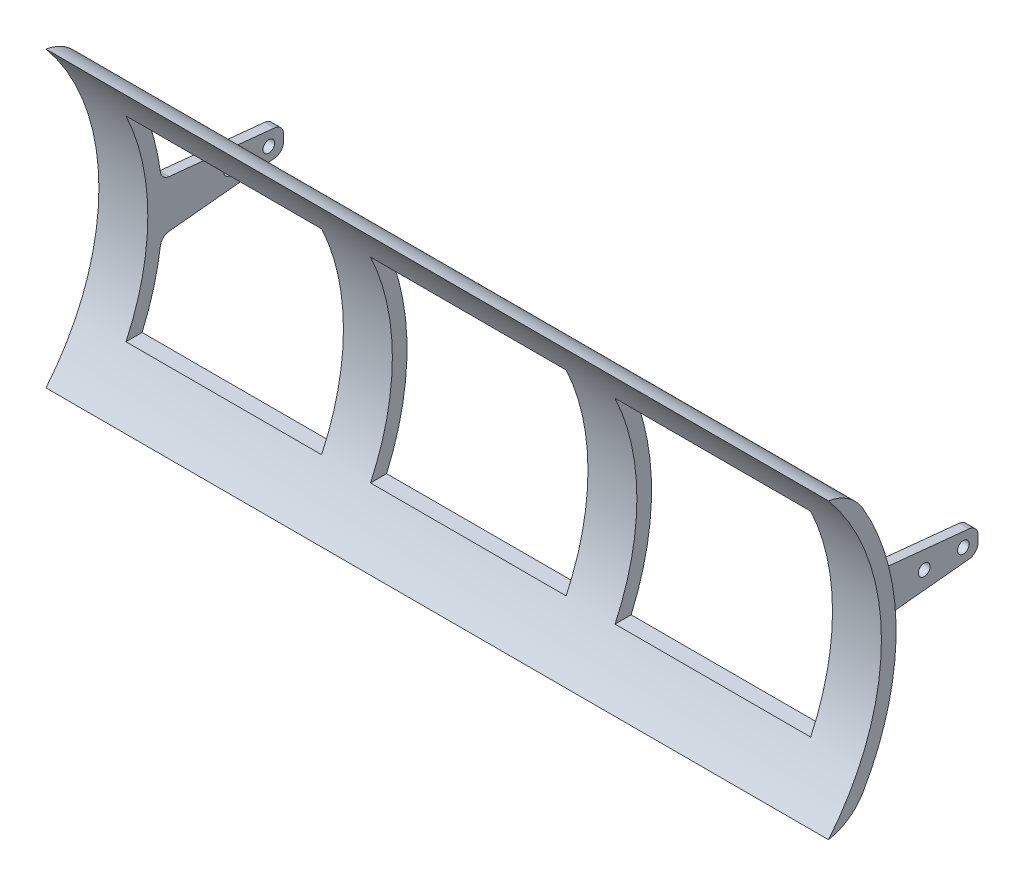
SolidWorks part; units mm, degrees
ref_plane "Front" through (0, 0, 0) normal (0, 0, 1) x (1, 0, 0)
ref_plane "Top" through (0, 0, 0) normal (0, 1, 0) x (1, 0, 0)
ref_plane "Right" through (0, 0, 0) normal (1, 0, 0) x (0, 0, -1)
sketch "Sketch1" plane through (0, 0, 0) normal (1, 0, 0) x (0, 0, -1)
  line L0 (50.8, -38.1) -> (45.9487, -38.1)
  line L1 (45.9487, 38.1) -> (50.8, 38.1)
  arc A0 (45.9487, 38.1) -> (45.9487, -38.1) centre (0, 0) cw
  arc A1 (50.8, 38.1) -> (50.8, -38.1) centre (0, 0) cw
  dimension "D1" = 59.69
  dimension "D3" = 63.5
  dimension "D2" = 76.2
extrude "Boss-Extrude1" add sketch "Sketch1" along normal mid plane 203.2
sketch "Sketch2" plane through (0, 0, 0) normal (0, 0, 1) x (1, 0, 0)
  line L0 (-38.1, -25.4) -> (-38.1, 25.4)
  line L1 (-88.9, -25.4) -> (-38.1, -25.4)
  line L2 (-88.9, -25.4) -> (-88.9, 25.4)
  line L3 (-88.9, 25.4) -> (-38.1, 25.4)
  line L4 (88.9, -25.4) -> (88.9, 25.4)
  line L7 (-25.4, -25.4) -> (-25.4, 25.4)
  line L8 (0, 25.4) -> (0, -25.4) construction
  line L9 (-25.4, -25.4) -> (25.4, -25.4)
  line L10 (-25.4, 25.4) -> (25.4, 25.4)
  line L11 (25.4, -25.4) -> (25.4, 25.4)
  line L12 (38.1, -25.4) -> (38.1, 25.4)
  line L13 (38.1, -25.4) -> (88.9, -25.4)
  line L14 (38.1, 25.4) -> (88.9, 25.4)
  point P0 (0, 0)
  dimension "D1" = 12.7
  dimension "D2" = 12.7
  dimension "D3" = 12.7
  dimension "D4" = 50.8
extrude "Cut-Extrude1" cut sketch "Sketch2" against normal through all
fillet "Fillet1" radius 12.7 2 edges at (0, 38.1, -50.8) (0, -38.1, -50.8)
sketch "Sketch6" plane through (88.9, 0, 0) normal (-1, 0, 0) x (0, 0, 1)
  line L0 (-63.1817, -6.35) -> (-94.9317, -3.175)
  line L1 (-94.9317, -3.175) -> (-94.9317, 3.175)
  line L2 (-94.9317, 3.175) -> (-63.1817, 6.35)
  line L3 (0, 0) -> (-94.9317, 0) construction
  arc A0 (-58.1987, 25.4) -> (-58.1987, -25.4) centre (0, 0) ccw construction
  arc A1 (-63.1817, 6.35) -> (-63.1817, -6.35) centre (0, 0) ccw
  arc A2 (-54.8717, 31.9585) -> (-54.8717, -31.9585) centre (0, 0) ccw construction
  circle A3 centre (-91.1217, 0) radius 1.524
  circle A4 centre (-80.9617, 0) radius 1.524
  dimension "D3" = 3.048
  dimension "D7" = 10.16
  dimension "D1" = 6.35
  dimension "D2" = 12.7
  dimension "D4" = 3.81
  dimension "D5" = 3.175
  dimension "D6" = 31.75
extrude "Boss-Extrude4" add sketch "Sketch6" against normal blind 2.54
mirror "Mirror2" about plane through (0, 0, 0) normal (1, 0, 0) of "Boss-Extrude4"
fillet "Fillet4" radius 2.54 10 edges at (-90.17, 3.175, -94.9317) (-90.17, -3.175, -94.9317) (-90.17, -6.35, -63.1817) (-90.17, 6.35, -63.1817) (-91.44, 0, -63.5) (90.17, -3.175, -94.9317) (90.17, 3.175, -94.9317) (91.44, 0, -63.5) (90.17, -6.35, -63.1817) (90.17, 6.35, -63.1817)
